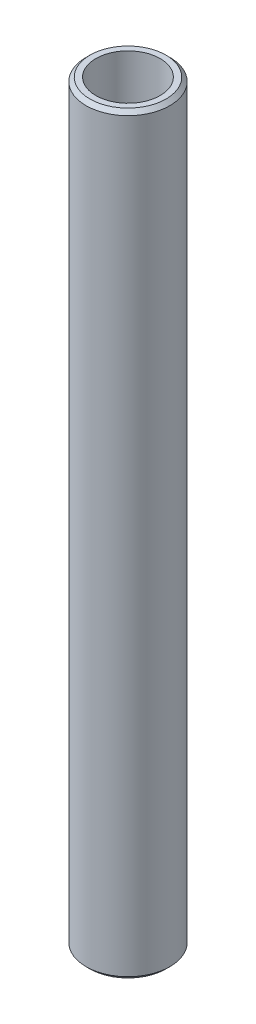
SolidWorks part; units mm, degrees
ref_plane "Front Plane" through (0, 0, 0) normal (0, 0, 1) x (1, 0, 0)
ref_plane "Top Plane" through (0, 0, 0) normal (0, 1, 0) x (1, 0, 0)
ref_plane "Right Plane" through (0, 0, 0) normal (1, 0, 0) x (0, 0, -1)
sketch "Sketch1" plane through (0, 0, 0) normal (0, 1, 0) x (1, 0, 0)
  circle A0 centre (0, 0) radius 30
  dimension "SHAFT_OD" = 60
extrude "Boss-Extrude1" add sketch "Sketch1" along normal blind 539.6114
sketch "Sketch2" plane through (0, 0, 0) normal (0, 1, 0) x (1, 0, 0)
  circle A0 centre (0, 0) radius 23.011
  dimension "BORE_D" = 46.0219
extrude "Cut-Extrude1" cut sketch "Sketch2" along normal through all
chamfer "Chamfer1" distance 2.7538 angle 45 2 edges at (0, 539.6114, 30) (0, 0, 30)
